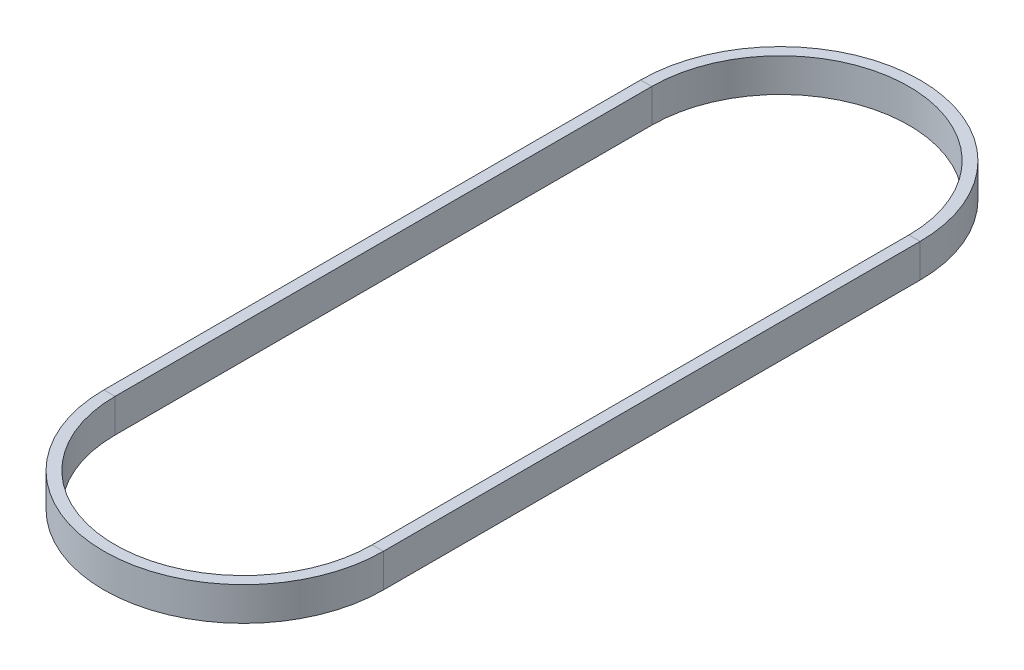
SolidWorks part; units mm, degrees
ref_plane "Front Plane" through (0, 0, 0) normal (0, 0, 1) x (1, 0, 0)
ref_plane "Top Plane" through (0, 0, 0) normal (0, 1, 0) x (1, 0, 0)
ref_plane "Right Plane" through (0, 0, 0) normal (1, 0, 0) x (0, 0, -1)
ref_axis "X" through (-88.99, 0, 0) along (1, 0, 0)
ref_axis "Y" through (0, 0, -88.99) along (0, 0, 1)
ref_axis "Z" through (0, 55, 0) along (0, -1, 0)
sketch "Sketch1" plane through (0, 0, 0) normal (0, 1, 0) x (1, 0, 0)
  line L0 (787.5224, -234.0111) -> (787.5224, -330.0111)
  line L1 (739.5224, -330.0111) -> (739.5224, -234.0111)
  arc A0 (787.5224, -234.0111) -> (739.5224, -234.0111) centre (763.5224, -234.0111) ccw
  arc A1 (739.5224, -330.0111) -> (787.5224, -330.0111) centre (763.5224, -330.0111) ccw
  point P2 (752.8529, -329.4163)
  point P4 (0, 0)
  point P7 (0, 0)
  point P8 (0, 0)
  point P10 (763.5224, -330.0111)
  point P11 (0, 0)
  point P16 (763.5224, -234.0111)
  dimension "D1" = 24
  dimension "D2" = 24
  dimension "D3" = 96
ref_plane "Plane1" through (739.5224, 0, 234.0111) normal (0, 0, -1) x (-1, 0, 0)
sketch "Sketch2" plane through (739.5224, 0, 234.0111) normal (0, 0, -1) x (-1, 0, 0)
  line L0 (0, 0) -> (-48, 0) construction
  line L1 (-1, 3) -> (1, 3)
  line L2 (-1, 3) -> (-1, -3)
  line L3 (-1, -3) -> (1, -3)
  line L4 (1, 3) -> (1, -3)
  line L5 (-1, 3) -> (1, -3) construction
  line L6 (-1, -3) -> (1, 3) construction
  point P0 (0, 0)
  dimension "D1" = 2
  dimension "D2" = 6
sweep "Sweep1" add profiles "Sketch2" path "Sketch1"
